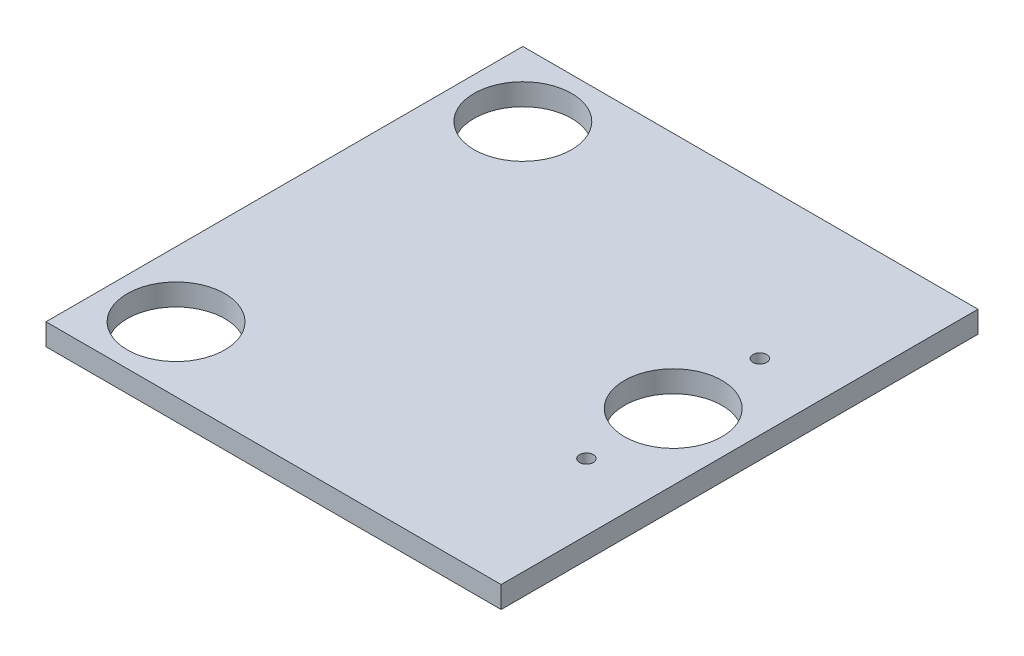
SolidWorks part; units mm, degrees
material "1060 Alloy"
ref_plane "Front Plane" through (0, 0, 0) normal (0, 0, 1) x (1, 0, 0)
ref_plane "Top Plane" through (0, 0, 0) normal (0, 1, 0) x (1, 0, 0)
ref_plane "Right Plane" through (0, 0, 0) normal (1, 0, 0) x (0, 0, -1)
sketch "Sketch1" plane through (0, 0, 0) normal (0, 1, 0) x (1, 0, 0)
  line L1 (0, -69.85) -> (133.35, -69.85)
  line L2 (0, -69.85) -> (0, 69.85)
  line L3 (0, 69.85) -> (133.35, 69.85)
  line L4 (133.35, -69.85) -> (133.35, 69.85)
  circle A3 centre (113.884, 25.3955) radius 2.0193
  circle A4 centre (113.884, -25.4045) radius 2.0193
  point P0 (0, 0)
  point P13 (0, 0)
  dimension "D1" = 139.7
  dimension "D5" = 133.35
extrude "Boss-Extrude1" add sketch "Sketch1" along normal blind 6.35
sketch "Sketch2" plane through (0, 0, 0) normal (0, 1, 0) x (1, 0, 0)
  line L0 (19.05, 50.8) -> (19.05, -50.8) construction
  line L5 (0, 69.85) -> (19.05, 50.8) construction
  line L6 (0, -69.85) -> (19.05, -50.8) construction
  line L7 (19.05, -50.8) -> (113.9007, 0) construction
  line L8 (113.9007, 0) -> (19.05, 50.8) construction
  line L9 (0, 69.85) -> (0, -69.85) construction
  line L10 (133.35, 69.85) -> (0, 69.85) construction
  line L11 (0, -69.85) -> (133.35, -69.85) construction
  line L12 (133.35, -69.85) -> (133.35, 69.85) construction
  circle A0 centre (19.05, 50.8) radius 14.2875
  circle A1 centre (19.05, -50.8) radius 14.2875
  circle A2 centre (113.9007, 0) radius 14.2875
  dimension "D2" = 28.575
  dimension "D1" = 19.05
  dimension "D6" = 19.4493
  dimension "D3" = 101.6
  dimension "D4" = 45
  dimension "D5" = 45
  dimension "D8" = 107.5979
  dimension "D9" = 107.5979
extrude "Cut-Extrude1" cut sketch "Sketch2" along normal through all
